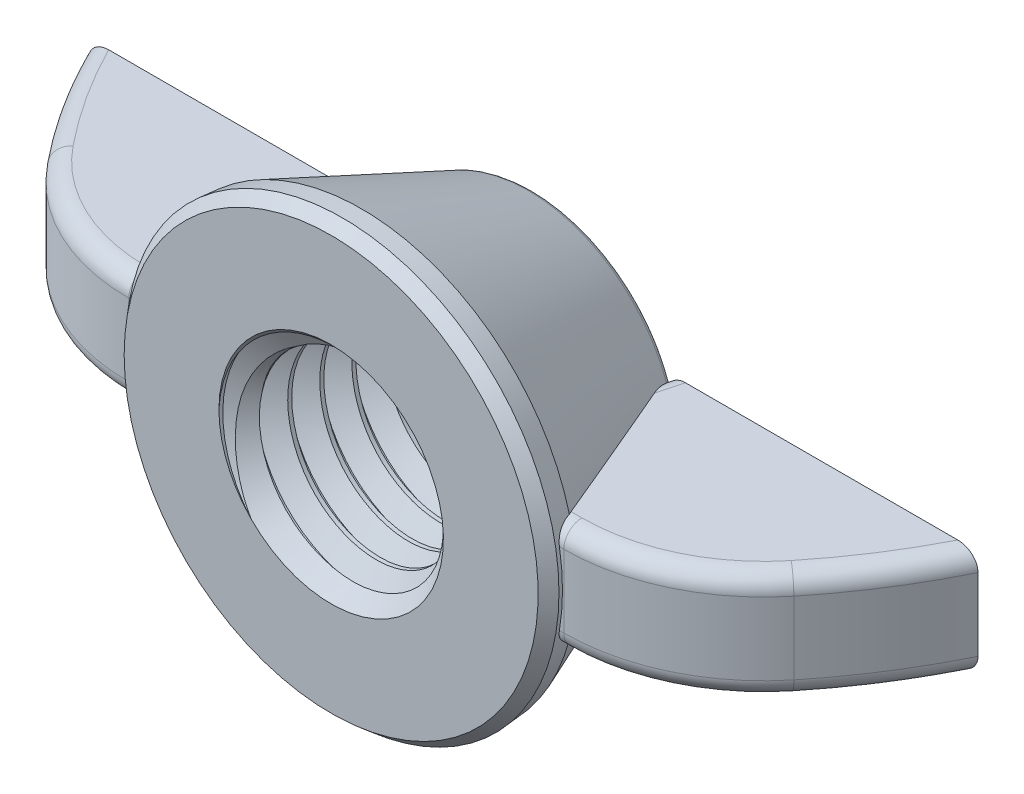
SolidWorks part; units mm, degrees
ref_plane "Front Plane" through (0, 0, 0) normal (0, 0, 1) x (1, 0, 0)
ref_plane "Top Plane" through (0, 0, 0) normal (0, 1, 0) x (1, 0, 0)
ref_plane "Right Plane" through (0, 0, 0) normal (1, 0, 0) x (0, 0, -1)
sketch "Sketch1" plane through (0, 0, 0) normal (0, 0, 1) x (1, 0, 0)
  circle A0 centre (0, 0) radius 3.175
  circle A1 centre (0, 0) radius 6.1516
  dimension "D1" = 12.3031
sketch "Sketch2" plane through (0, 0, 0) normal (0, 1, 0) x (1, 0, 0)
  line L0 (0, 0) -> (0, 15.875) construction
  line L1 (-3.175, 0) -> (3.175, 0) construction
  line L2 (-14.2875, 15.875) -> (14.2875, 15.875) construction
  line L3 (14.2875, 15.875) -> (14.2875, 0) construction
  line L4 (-14.2875, 15.875) -> (-14.2875, 0) construction
  line L5 (-14.2875, 0) -> (14.2875, 0) construction
  line L6 (-4.1928, 5.715) -> (4.1928, 5.715) construction
  line L7 (0, 0) -> (0, 5.715) construction
  line L8 (-4.3144, 0.8572) -> (6.1516, 0.8572) construction
  line L9 (6.1516, 0) -> (6.1516, 5.715) construction
  line L10 (3.7735, 5.715) -> (6.5552, 16.0963)
  line L12 (4.1928, 5.715) -> (4.1928, 0.4286) construction
  line L13 (-6.1516, 0) -> (6.1516, 0) construction
  line L14 (6.1516, 0.8572) -> (4.1928, 5.715) construction
  line L15 (6.5552, 16.0963) -> (14.6189, 13.631)
  line L16 (14.6189, 13.631) -> (8.5296, 0.4286)
  line L17 (6.1516, 0.4286) -> (8.5296, 0.4286)
  line L19 (3.7735, 0.4286) -> (6.1516, 0.4286)
  line L20 (-3.7735, 5.715) -> (3.7735, 5.715) construction
  line L21 (3.7735, 5.715) -> (3.7735, 0.4286)
  circle A3 centre (13.4331, 13.1001) radius 0.8544 construction
  circle A4 centre (7.1515, 15.0206) radius 0.8544 construction
  dimension "D6" = 1.7088
  dimension "D2" = 5.715
  dimension "D4" = 8.3857
  dimension "D1" = 0.8572
  dimension "D3" = 21.96
  dimension "D5" = 0.4286
  dimension "D8" = 17
  dimension "D9" = 7.5471
  dimension "D7" = 15
sketch "Sketch13" plane through (0, 0, 0) normal (0, 1, 0) x (1, 0, 0)
  line L1 (3.7735, 5.715) -> (3.7735, 0.4286) construction
  line L2 (3.7735, 5.715) -> (6.5552, 16.0963) construction
  line L3 (-14.2875, 15.875) -> (14.2875, 15.875) construction
  line L4 (14.2875, 15.875) -> (14.2875, 0) construction
  line L5 (6.1516, 0.4286) -> (8.5296, 0.4286) construction
  line L6 (3.7735, 0.4286) -> (6.1516, 0.4286) construction
  line L7 (0, 0) -> (0, 5.715) construction
  line L8 (-3.175, 0) -> (3.175, 0) construction
  line L9 (0, 0) -> (0, 15.875) construction
  line L10 (-4.1928, 5.715) -> (4.1928, 5.715) construction
  line L11 (3.7735, 0.4286) -> (6.1516, 0.4286)
  line L12 (3.7735, 5.715) -> (3.7735, 0.4286)
  line L13 (3.7735, 5.715) -> (6.3262, 15.2417)
  circle A0 centre (13.4331, 13.1001) radius 0.8544 construction
  circle A1 centre (7.1515, 15.0206) radius 0.8544 construction
  arc A5 (14.2875, 13.1001) -> (13.9109, 13.8084) centre (13.4331, 13.1001) ccw
  arc A6 (7.1515, 15.875) -> (6.3262, 15.2417) centre (7.1515, 15.0206) ccw
  arc A7 (10.5535, 2.5321) -> (14.2875, 13.1001) centre (-2.5346, 13.1001) ccw
  arc A8 (13.9109, 13.8084) -> (7.1515, 15.875) centre (7.1515, 3.7873) ccw
  arc A10 (6.1516, 0.4286) -> (10.5535, 2.5321) centre (6.1516, 6.0864) ccw
extrude "Extrude2" add sketch "Sketch13" along normal mid plane 3.0758
sketch "Sketch3" plane through (0, 0, 0) normal (0, 0, 1) x (1, 0, 0)
  circle A0 centre (0, 0) radius 6.1516 construction
  circle A1 centre (0, 0) radius 6.1516
extrude "Extrude1" add sketch "Sketch3" against normal up to vertex (0.8572 mm away) draft 5 separate body up to point (6.1516, 0, -0.8572)
sketch "Sketch15" plane through (0, 0, -0.8572) normal (0, 0, -1) x (-1, 0, 0)
  circle A1 centre (0, 0) radius 6.0766
  circle A2 centre (0, 0) radius 6.0766
  dimension "D1" = 0
extrude "Extrude3" add sketch "Sketch15" along normal up to vertex (4.8578 mm away) draft 21.96 up to point (0, 0, -5.715)
fillet "Fillet3" radius 0.254 1 edges at (-4.1178, 0, -5.715)
sketch "Sketch12" plane through (0, 0, -5.715) normal (0, 0, -1) x (-1, 0, 0)
  circle A1 centre (0, 0) radius 6.0766
  circle A2 centre (0, 0) radius 6.0766 construction
  dimension "D1" = 12.1531
sketch "Sketch4" plane through (0, 0, 0) normal (0, 0, 1) x (1, 0, 0)
  circle A0 centre (0, 0) radius 3.175 construction
  circle A1 centre (0, 0) radius 3.175
extrude "Cut-Extrude1" cut sketch "Sketch4" against normal through all
sketch "Sketch5" plane through (0, 0, 0) normal (0, 0, 1) x (1, 0, 0)
  circle A0 centre (0, 0) radius 3.175 construction
  circle A1 centre (0, 0) radius 3.175
curve "Helix/Spiral1" pitch 0.9071 height 8.89 turns 9.8 parameters "pitch"=0.9071
sketch "Sketch6" plane through (0, 0, 0) normal (0, 1, 0) x (1, 0, 0)
  line L0 (-3.175, -0.7937) -> (-2.5858, -0.4536)
  line L1 (-2.5858, -0.4536) -> (-2.5858, -0.3402)
  line L2 (-2.5858, -0.3402) -> (-3.175, 0)
  line L3 (-3.175, -0.7937) -> (-3.175, 0)
  line L4 (-3.175, -0.3969) -> (-2.5858, -0.3969) construction
  line L5 (-2.8804, -0.6237) -> (-2.8804, -0.1701) construction
  line L6 (-3.175, 0) -> (3.175, 0) construction
  dimension "D1" = 60
  dimension "D2" = 0.1134
  dimension "D3" = 0.4536
sweep "Sweep1" add profiles "Sketch6" path "Helix/Spiral1"
sketch "Sketch7" plane through (0, 0, 0) normal (0, 0, 1) x (1, 0, 0)
  circle A1 centre (0, 0) radius 6.1516
  circle A2 centre (0, 0) radius 6.1516
  dimension "D1" = 0
extrude "Cut-Extrude2" cut sketch "Sketch7" along normal through all
ref_plane "Plane1" through (0, 0, -5.715) normal (0, 0, 1) x (1, 0, 0)
sketch "Sketch8" plane through (0, 0, -5.715) normal (0, 0, 1) x (1, 0, 0)
  circle A0 centre (0, 0) radius 6.0766 construction
  circle A2 centre (0, 0) radius 6.0766
extrude "Cut-Extrude3" cut sketch "Sketch8" against normal through all
sketch "Sketch9" plane through (0, 0, 0) normal (0, 0, 1) x (1, 0, 0)
  circle A1 centre (0, 0) radius 3.175
  circle A2 centre (0, 0) radius 3.175
  dimension "D1" = 0
extrude "Cut-Extrude4" cut sketch "Sketch9" against normal through all draft 45
sketch "Sketch11" plane through (0, 0, -5.715) normal (0, 0, 1) x (1, 0, 0)
  circle A0 centre (0, 0) radius 3.175 construction
  circle A1 centre (0, 0) radius 3.1242
  circle A2 centre (0, 0) radius 3.175 construction
  dimension "D1" = 0.0508
extrude "Cut-Extrude5" cut sketch "Sketch11" along normal through all draft 45
chamfer "Chamfer1" distance 0.3215 angle 45 1 edges at (6.1516, 0, 0) first distance on face at (-6.0766, 0, -0.8572)
fillet "Fillet4" radius 0.5126 14 edges at (4.9626, 1.5379, -0.4286) (8.5909, 1.5379, -0.9815) (6.6314, 1.5379, -15.6984) (10.6856, 1.5379, -15.3468) (14.1875, 1.5379, -13.5012) (4.9626, -1.5379, -0.4286) (8.5909, -1.5379, -0.9815) (6.6314, -1.5379, -15.6984) (10.6856, -1.5379, -15.3468) (14.1875, -1.5379, -13.5012) (13.3266, 1.5379, -7.496) (13.3266, -1.5379, -7.496) (5.0499, 1.5379, -10.4784) (5.0499, -1.5379, -10.4784)
mirror "Mirror6" about plane through (0, 0, 0) normal (1, 0, 0) of bodies 108 113
combine bodies "Combine2" operation type add bodies to combine 116 108 107
sketch "Sketch16" plane through (0, 0, -5.715) normal (0, 0, -1) x (-1, 0, 0)
  circle A0 centre (0, 0) radius 15.7966
extrude "Cut-Extrude6" cut sketch "Sketch16" along normal through all
equation "\"D1@Sketch1\" = \"thread dia@Sketch1\"*1.725"
equation "\"D2@Sketch2\" = \"B@Sketch2\"*.36"
equation "\"D3@Helix/Spiral1\" = \"D2@Sketch2\"+.125"
equation "\"D2@Sketch6\" = \"pitch@Helix/Spiral1\"*.125"
equation "\"D3@Sketch6\" = \"pitch@Helix/Spiral1\"*.5"
equation "\"D4@Sketch2\" = \"D1@Sketch12\"*.69"
equation "\"D1@Extrude2\" = \"D1@Sketch1\"*.25"
equation "\"D1@Sketch2\" = \"D2@Sketch2\"*.150"
equation "\"D5@Sketch2\" = \"D1@Sketch2\"/2"
equation "\"D3@Extrude3\" = \"D3@Sketch2\""
equation "\"D1@Chamfer1\" = \"D5@Sketch2\"*.75"
equation "\"D9@Sketch2\" = \"D4@Sketch2\"*.9"
equation "\"D6@Sketch2\" = \"D1@Extrude2\"/1.8"
equation "\"D1@Fillet4\" = \"D1@Extrude2\"/6"
